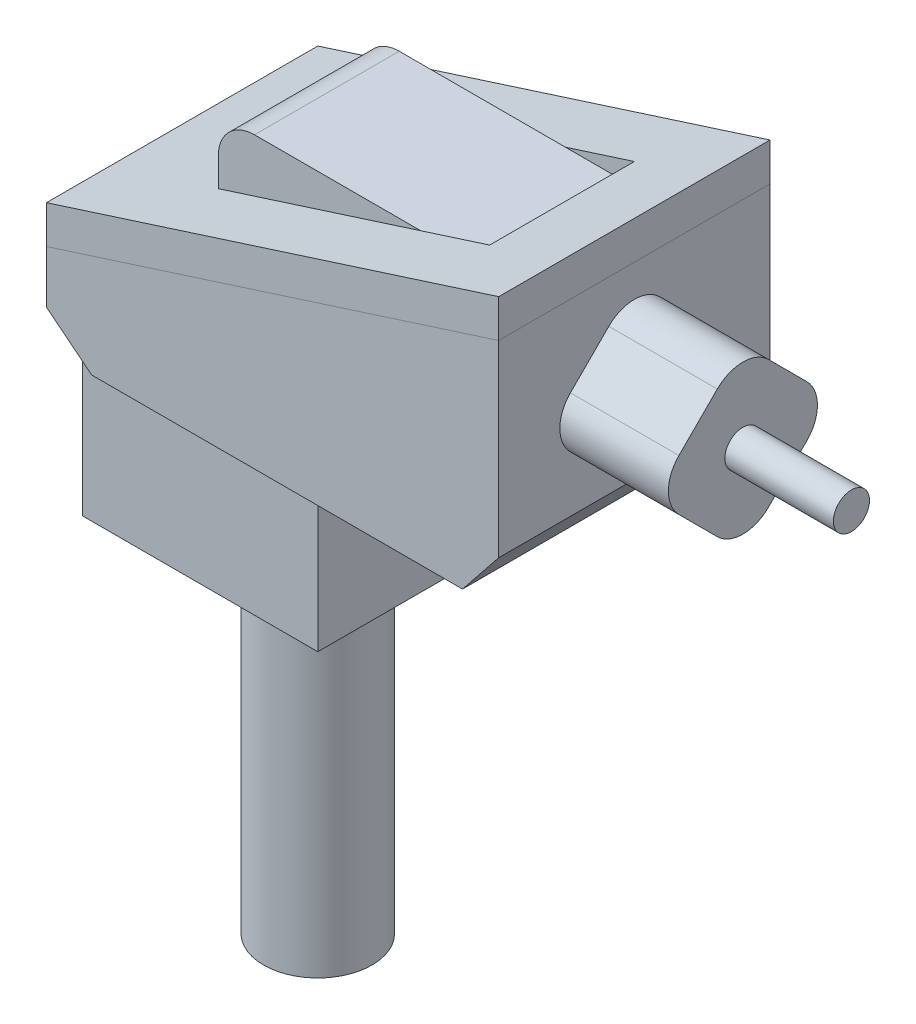
SolidWorks part; units mm, degrees
material "ABS"
ref_plane "Plan de face" through (0, 0, 0) normal (0, 0, 1) x (1, 0, 0)
ref_plane "Plan de dessus" through (0, 0, 0) normal (0, 1, 0) x (1, 0, 0)
ref_plane "Plan de droite" through (0, 0, 0) normal (1, 0, 0) x (0, 0, -1)
sketch "Esquisse1" plane through (0, 0, 0) normal (0, 1, 0) x (1, 0, 0)
  circle A0 centre (0, 0) radius 3
  dimension "D1" = 6
extrude "Boss.-Extru.1" add sketch "Esquisse1" against normal blind 20
sketch "Esquisse2" plane through (0, 0, 0) normal (0, 1, 0) x (1, 0, 0)
  line L1 (-6.5, -6.5) -> (6.5, -6.5)
  line L2 (-6.5, -6.5) -> (-6.5, 6.5)
  line L3 (-6.5, 6.5) -> (6.5, 6.5)
  line L4 (6.5, -6.5) -> (6.5, 6.5)
  line L5 (-6.5, -6.5) -> (6.5, 6.5) construction
  line L6 (-6.5, 6.5) -> (6.5, -6.5) construction
  point P0 (0, 0)
  dimension "D1" = 13
extrude "Boss.-Extru.2" add sketch "Esquisse2" along normal blind 8
sketch "Esquisse3" plane through (0, 0, 0) normal (0, 0, 1) x (1, 0, 0)
  line L0 (-7.5, 15) -> (-7.5, 10)
  line L1 (-7.5, 10) -> (-5, 8)
  line L2 (-5, 8) -> (15.5, 8)
  line L3 (15.5, 8) -> (17.5, 10.5)
  line L4 (17.5, 10.5) -> (17.5, 23)
  line L5 (17.5, 23) -> (-7.5, 15)
  line L7 (-6.5, 8) -> (-6.5, 0) construction
  dimension "D1" = 2.5
  dimension "D2" = 2
  dimension "D3" = 2
  dimension "D4" = 2.5
  dimension "D5" = 1
  dimension "D6" = 25
  dimension "D7" = 15
  dimension "D8" = 7
extrude "Boss.-Extru.3" add sketch "Esquisse3" along normal mid plane 15
sketch "Esquisse4" plane through (0, 0, 0) normal (0, 0, 1) x (1, 0, 0)
  line L0 (17.5, 23) -> (-7.5, 15) construction
  line L1 (9.6875, 20.5) -> (-1.5, 20.5)
  line L2 (9.6875, 20.5) -> (9.6875, 16.92)
  line L3 (9.6875, 16.92) -> (-1.5, 16.92)
  line L4 (-1.5, 20.5) -> (-1.5, 16.92)
  line L5 (-7.5, 15) -> (-7.5, 10) construction
  line L6 (-5, 8) -> (15.5, 8) construction
  dimension "D1" = 6
  dimension "D2" = 12.5
extrude "Boss.-Extru.4" add sketch "Esquisse4" along normal mid plane 8
sketch "Esquisse5" plane through (0, 20.5, 0) normal (0, 1, 0) x (1, 0, 0)
  line L0 (-1.5, -4) -> (9.6875, -4) construction
  line L1 (-1.5, 4) -> (13.5, 4)
  line L2 (-1.5, 4) -> (-1.5, -4)
  line L3 (-1.5, -4) -> (13.5, -4)
  line L4 (13.5, 4) -> (13.5, -4)
  dimension "D1" = 15
extrude "Enlèv. mat.-Extru.1" cut sketch "Esquisse5" along normal through all
sketch "Esquisse6" plane through (17.5, 0, 0) normal (1, 0, 0) x (0, 0, -1)
  line L0 (-4.9497, 15) -> (0, 10.0503)
  line L1 (-4.9497, 15) -> (0, 19.9497)
  line L2 (0, 10.0503) -> (4.9497, 15)
  line L3 (0, 19.9497) -> (4.9497, 15)
  line L4 (-7.5, 8) -> (7.5, 8) construction
  line L5 (-7.5, 23) -> (7.5, 23) construction
  dimension "D1" = 7
  dimension "D2" = 7
  dimension "D3" = 8
extrude "Boss.-Extru.5" add sketch "Esquisse6" along normal blind 6
sketch "Esquisse7" plane through (23.5, 0, 0) normal (1, 0, 0) x (0, 0, -1)
  circle A0 centre (0, 15) radius 1
  dimension "D1" = 2
extrude "Boss.-Extru.6" add sketch "Esquisse7" along normal blind 6
fillet "Congé1" radius 2 5 edges at (-1.5, 20.5, 0) (20.5, 10.0503, 0) (20.5, 15, -4.9497) (20.5, 19.9497, 0) (20.5, 15, 4.9497)
sketch "Esquisse8" plane through (0, 0, 7.5) normal (0, 0, 1) x (1, 0, 0)
  line L0 (-7.5, 12.9001) -> (17.5, 20.9001)
  line L1 (-7.5, 15) -> (-7.5, 10) construction
  line L2 (17.5, 10.5) -> (17.5, 23) construction
  line L3 (17.5, 23) -> (-7.5, 15) construction
  dimension "D1" = 2
split "Fractionner1" trim tools "Esquisse8" bodies to split 107 resulting bodies 108 109
